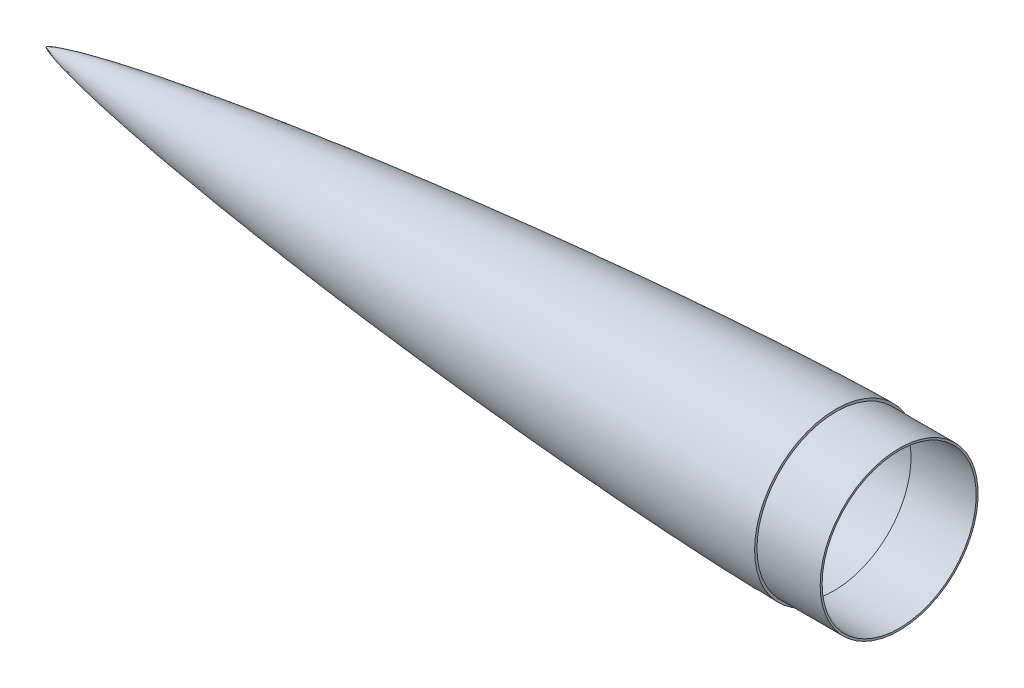
SolidWorks part; units mm, degrees
ref_plane "Front Plane" through (0, 0, 0) normal (0, 0, 1) x (1, 0, 0)
ref_plane "Top Plane" through (0, 0, 0) normal (0, 1, 0) x (1, 0, 0)
ref_plane "Right Plane" through (0, 0, 0) normal (1, 0, 0) x (0, 0, -1)
sketch "Sketch1" plane through (0, 0, 0) normal (0, 0, 1) x (1, 0, 0)
  line L0 (0, 0) -> (685.8, 0)
  line L1 (55.2447, 0) -> (-55.2447, 0) construction
  line L2 (685.8, 63.5) -> (635, 63.5)
  line L3 (635, 63.5) -> (635, 65.405)
  line L4 (685.8, 63.5) -> (685.8, 0)
  spline S0 degree 4 poles (0, 0) (0.0022, 0.0063) (0.0075, 0.0184) (0.0223, 0.0404) (0.057, 0.0804) (0.1098, 0.1304) (0.1816, 0.1889) (0.2836, 0.2634) (0.4063, 0.3444) (0.5502, 0.4318) (0.7155, 0.5251) (0.9567, 0.6537) (1.3318, 0.8391) (1.9703, 1.1275) (3.1158, 1.5922) (5.1634, 2.3284) (8.9332, 3.5155) (16.022, 5.4463) (28.2617, 8.305) (49.1788, 12.5136) (77.9573, 17.4873) (112.8708, 22.8061) (151.8575, 28.1242) (190.9036, 32.9827) (229.9952, 37.4592) (269.1232, 41.6038) (308.2821, 45.4454) (347.4678, 49.0026) (386.6776, 52.2836) (425.9094, 55.2895) (465.1619, 58.0128) (504.4341, 60.4362) (538.8141, 62.2665) (568.2945, 63.5925) (591.9899, 64.4666) (607.8766, 64.942) (620.8678, 65.2384) (628.9431, 65.3608) (632.981, 65.3999) (635, 65.405) knots 0 0 0 0 0 0.000041 0.000083 0.000165 0.000331 0.000496 0.000661 0.000955 0.001249 0.001549 0.001849 0.002664 0.003866 0.00593 0.009578 0.01627 0.028579 0.051871 0.088176 0.149698 0.211221 0.272743 0.334265 0.395788 0.45731 0.518832 0.580355 0.641877 0.703399 0.764922 0.826444 0.887966 0.918727 0.949489 0.974744 0.987372 1 1 1 1 1 construction
  spline S1 degree 4 poles (0, 0) (0.0022, 0.0063) (0.0075, 0.0184) (0.0223, 0.0404) (0.057, 0.0804) (0.1098, 0.1304) (0.1816, 0.1889) (0.2836, 0.2634) (0.4063, 0.3444) (0.5502, 0.4318) (0.7155, 0.5251) (0.9567, 0.6537) (1.3318, 0.8391) (1.9703, 1.1275) (3.1158, 1.5922) (5.1634, 2.3284) (8.9332, 3.5155) (16.022, 5.4463) (28.2617, 8.305) (49.1788, 12.5136) (77.9573, 17.4873) (112.8708, 22.8061) (151.8575, 28.1242) (190.9036, 32.9827) (229.9952, 37.4592) (269.1232, 41.6038) (308.2821, 45.4454) (347.4678, 49.0026) (386.6776, 52.2836) (425.9094, 55.2895) (465.1619, 58.0128) (504.4341, 60.4362) (538.8141, 62.2665) (568.2945, 63.5925) (591.9899, 64.4666) (607.8766, 64.942) (620.8678, 65.2384) (628.9431, 65.3608) (632.981, 65.3999) (635, 65.405) knots 0 0 0 0 0 0.000041 0.000083 0.000165 0.000331 0.000496 0.000661 0.000955 0.001249 0.001549 0.001849 0.002664 0.003866 0.00593 0.009578 0.01627 0.028579 0.051871 0.088176 0.149698 0.211221 0.272743 0.334265 0.395788 0.45731 0.518832 0.580355 0.641877 0.703399 0.764922 0.826444 0.887966 0.918727 0.949489 0.974744 0.987372 1 1 1 1 1
  dimension "D1" = 635
  dimension "D2" = 50.8
  dimension "D3" = 63.5
  dimension "D4" = 65.405
revolve "Revolve1" add sketch "Sketch1" angle 360 about L0
shell "Shell1" thickness 1.5875 removed face at (685.8, 0, 63.5)
equation "\"D_o\"= 5.15in"
equation "\"D_i\"= 5in"
equation "\"D_c\"= 4.8in"
equation "\"L\"= 25in"
equation "\"L_s\"= 2in"
equation "\"D2@Sketch1\"=\"L_s\""
equation "\"D1@Sketch1\"=\"L\""
equation "\"D3@Sketch1\"=\"D_i\"/2"
equation "\"D4@Sketch1\"=\"D_o\"/2"
